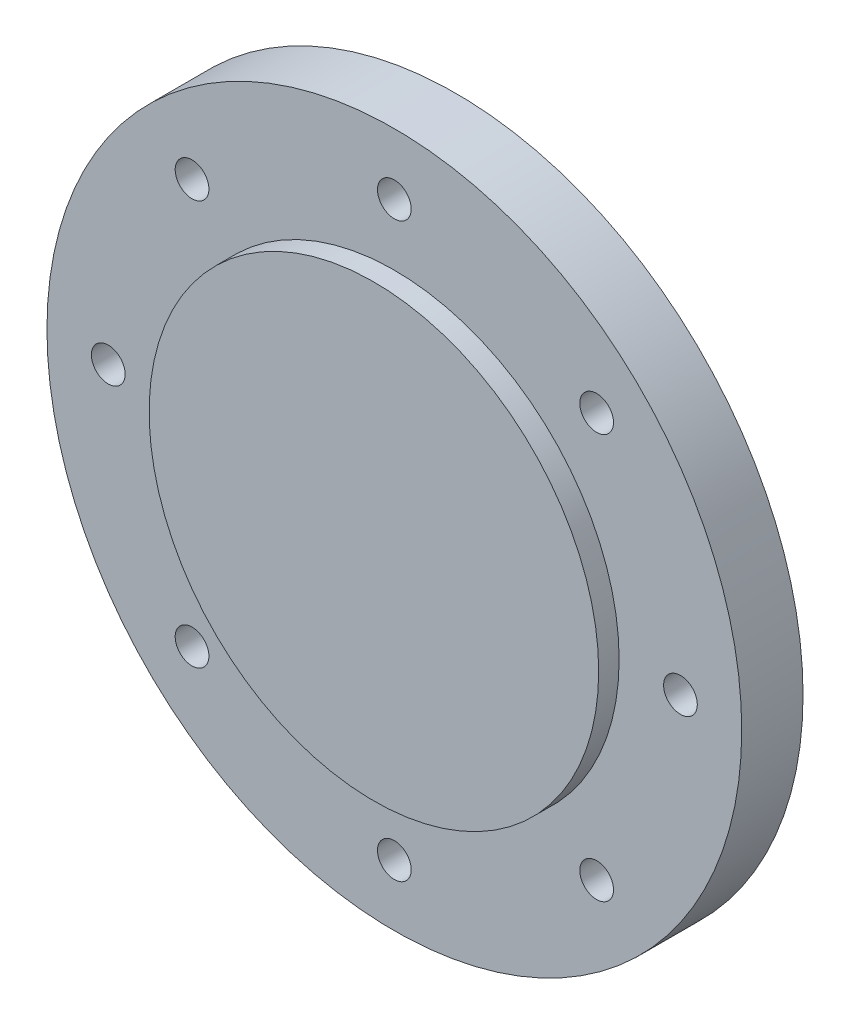
SolidWorks part; units mm, degrees
ref_plane "Front Plane" through (0, 0, 0) normal (0, 0, 1) x (1, 0, 0)
ref_plane "Top Plane" through (0, 0, 0) normal (0, 1, 0) x (1, 0, 0)
ref_plane "Right Plane" through (0, 0, 0) normal (1, 0, 0) x (0, 0, -1)
sketch "SK_Disc" plane through (0, 0, 0) normal (0, 0, 1) x (1, 0, 0)
  circle A0 centre (0, 0) radius 34
  dimension "D_disc" = 68
extrude "Output_Disc" add sketch "SK_Disc" along normal blind 6
ref_plane "PL_Mount" through (0, 0, 6) normal (0, 0, 1) x (1, 0, 0)
sketch "SK_Pilot" plane through (0, 0, 6) normal (0, 0, 1) x (1, 0, 0)
  circle A0 centre (0, 0) radius 22
  dimension "D_pil" = 44
extrude "Pilot_Boss" add sketch "SK_Pilot" along normal blind 2
sketch "SK_OutHole" plane through (0, 0, 6) normal (0, 0, 1) x (1, 0, 0)
  circle A0 centre (28, 0) radius 1.65
  dimension "D_oh" = 3.3
  dimension "R_oh" = 28
extrude "Output_Tapped_Hole" cut sketch "SK_OutHole" against normal blind 6
ref_axis "AX_Joint" through (0, 0, -0.4) along (0, 0, 1)
pattern_circular "Output_Hole_Pattern" count 8 over 360 about axis through (0, 0, -0.4) along (0, 0, 1) of "Output_Tapped_Hole"
equation "\"D_out\" = 68"
equation "\"T_out\" = 6"
equation "\"PCD_out\" = 56"
equation "\"D_pilot\" = 44"
equation "\"H_pilot\" = 2"
equation "\"D_out_hole\" = 3.3"
equation "\"D_disc@SK_Disc\" = \"D_out\""
equation "\"D1@Output_Disc\" = \"T_out\""
equation "\"D_pil@SK_Pilot\" = \"D_pilot\""
equation "\"D1@Pilot_Boss\" = \"H_pilot\""
equation "\"D_oh@SK_OutHole\" = \"D_out_hole\""
equation "\"R_oh@SK_OutHole\" = \"PCD_out\"/2"
